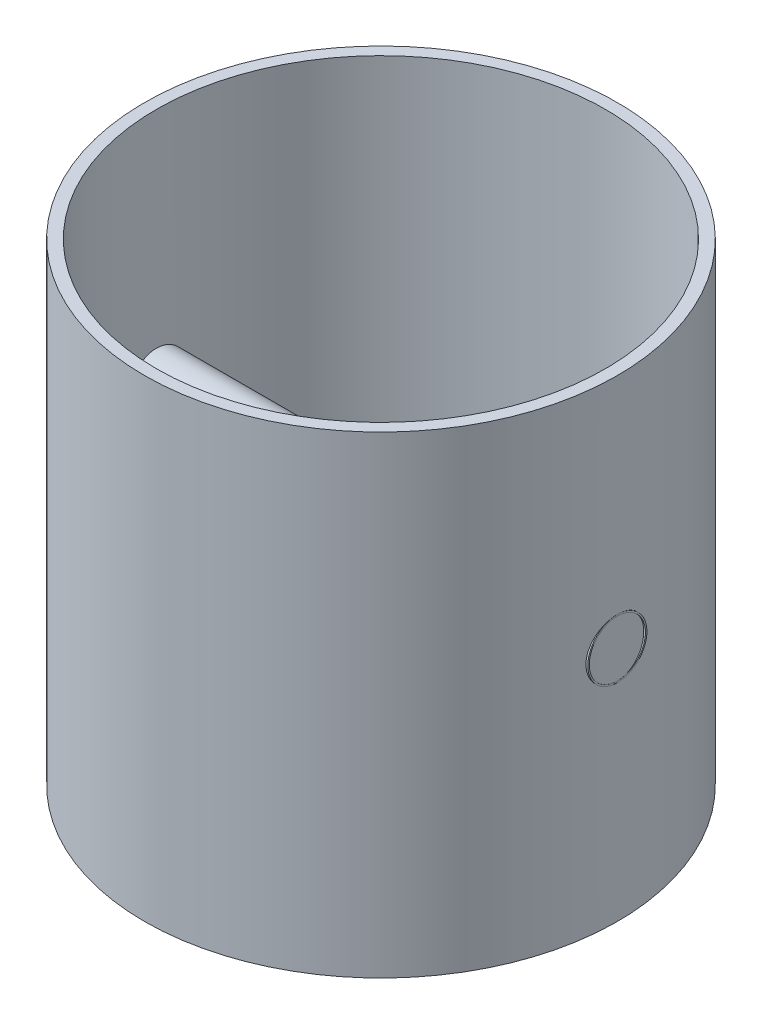
SolidWorks part; units mm, degrees
material "Head"
ref_plane "Front Plane" through (0, 0, 0) normal (0, 0, 1) x (1, 0, 0)
ref_plane "Top Plane" through (0, 0, 0) normal (0, 1, 0) x (1, 0, 0)
ref_plane "Right Plane" through (0, 0, 0) normal (1, 0, 0) x (0, 0, -1)
sketch "Sketch1" plane through (0, 0, 0) normal (0, 1, 0) x (1, 0, 0)
  circle A0 centre (0, 0) radius 20
extrude "Boss-Extrude1" add sketch "Sketch1" along normal blind 40
sketch "Sketch2" plane through (0, 40, 0) normal (0, 1, 0) x (1, 0, 0)
  circle A0 centre (0, 0) radius 19
  dimension "D1" = 38
extrude "Cut-Extrude1" cut sketch "Sketch2" against normal blind 39
ref_axis "Axis1" through (0, -51.9859, 0) along (0, 1, 0)
sketch "Sketch5" plane through (0, 0, 0) normal (1, 0, 0) x (0, 0, -1)
  line L0 (0, -51.9859) -> (0, 92.9624) construction
  line L1 (-20, 0) -> (20, 0) construction
  circle A0 centre (0, 20) radius 2.5
  circle A1 centre (0, 20) radius 2.375
  dimension "D1" = 20
  dimension "D2" = 4.75
extrude "Boss-Extrude2" add sketch "Sketch5" along normal through all and the other way through all
